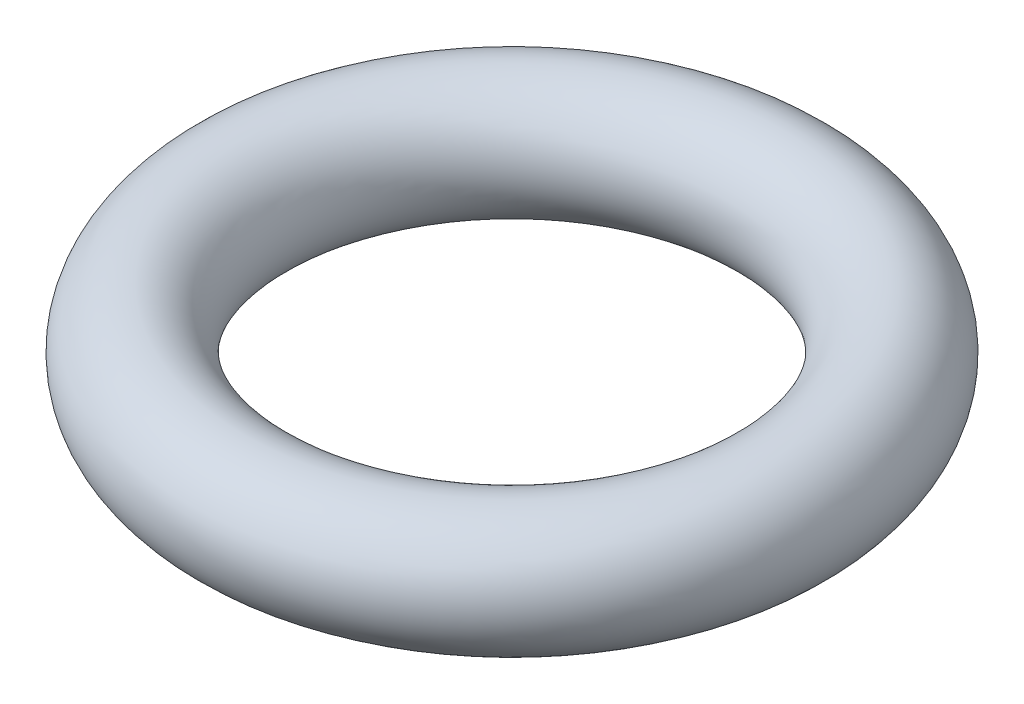
SolidWorks part; units mm, degrees
ref_plane "Front Plane" through (0, 0, 0) normal (0, 0, 1) x (1, 0, 0)
ref_plane "Top Plane" through (0, 0, 0) normal (0, 1, 0) x (1, 0, 0)
ref_plane "Right Plane" through (0, 0, 0) normal (1, 0, 0) x (0, 0, -1)
sketch "Sketch1" plane through (0, 0, 0) normal (0, 1, 0) x (1, 0, 0)
  circle A1 centre (0, 0) radius 3.035
  dimension "B" = 6.07
sketch "Sketch2" plane through (0, 0, 0) normal (0, 0, 1) x (1, 0, 0)
  circle A0 centre (-3.925, 0) radius 0.89
  point P4 (-3.035, 0)
  dimension "A" = 1.78
sweep "Sweep1" add profiles "Sketch2" path "Sketch1"
ref_axis "Axis1" through (0, 5.2562, 0) along (0, -1, 0)
